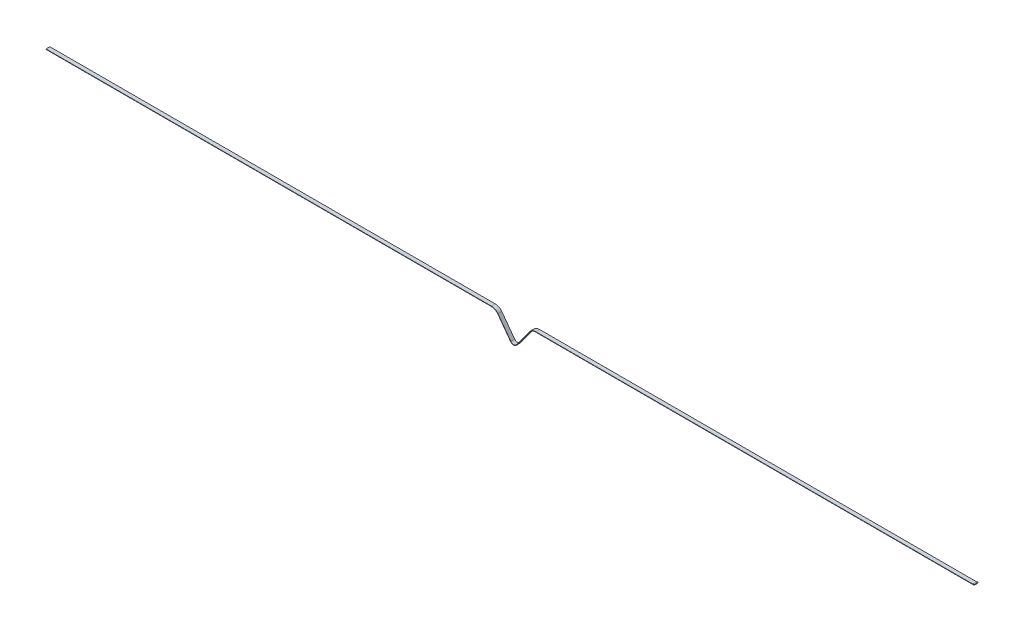
SolidWorks part; units mm, degrees
ref_plane "Front Plane" through (0, 0, 0) normal (0, 0, 1) x (1, 0, 0)
ref_plane "Top Plane" through (0, 0, 0) normal (0, 1, 0) x (1, 0, 0)
ref_plane "Right Plane" through (0, 0, 0) normal (1, 0, 0) x (0, 0, -1)
sketch "Sketch1" plane through (0, 0, 0) normal (1, 0, 0) x (0, 0, -1)
  line L1 (0, 0) -> (6, 0)
  line L2 (0, 0) -> (0, 0.63)
  line L3 (0, 0.63) -> (6, 0.63)
  line L4 (6, 0) -> (6, 0.63)
  dimension "D1" = 0.63
  dimension "D2" = 6
sketch "Sketch2" plane through (0, 0, 0) normal (0, 0, 1) x (1, 0, 0)
  line L0 (0, 0) -> (-683.7729, 0)
  line L1 (-693.4055, -4.8779) -> (-713.4177, -32.1359)
  line L2 (-723.268, -32.1359) -> (-743.2802, -4.8779)
  line L3 (-752.9129, 0) -> (-1447.8, 0)
  arc A0 (-683.7729, 0) -> (-693.4055, -4.8779) centre (-683.7729, -11.95) ccw
  arc A1 (-713.4177, -32.1359) -> (-723.268, -32.1359) centre (-718.3429, -28.52) cw
  arc A2 (-743.2802, -4.8779) -> (-752.9129, 0) centre (-752.9129, -11.95) ccw
  dimension "D1" = 6.11
  dimension "D4" = 1447.8
sweep "Sweep1" add profiles "Sketch1" path "Sketch2"
sketch "Sketch3" plane through (0, 0, 0) normal (0, 0, 1) x (1, 0, 0)
  line L0 (0, 0.63) -> (-683.7729, 0.63) construction
  line L1 (-1.5, 0.63) -> (-1.5, 0)
  line L2 (0, 0) -> (-683.7729, 0) construction
  line L3 (-1.5, 0) -> (0, 0)
  line L4 (0, 0) -> (0, 0.63)
  arc A1 (0, 0.63) -> (-1.5, 0.63) centre (-0.75, 0.63) ccw
  dimension "D1" = 0.75
extrude "Boss-Extrude1" add sketch "Sketch3" against normal through all
pattern_curve "CrvPattern1" [suppressed] of bodies 102 driven by "Sketch2" parameters "D1"=2000, "D3"=2, "D2"=1, "D4"=10
